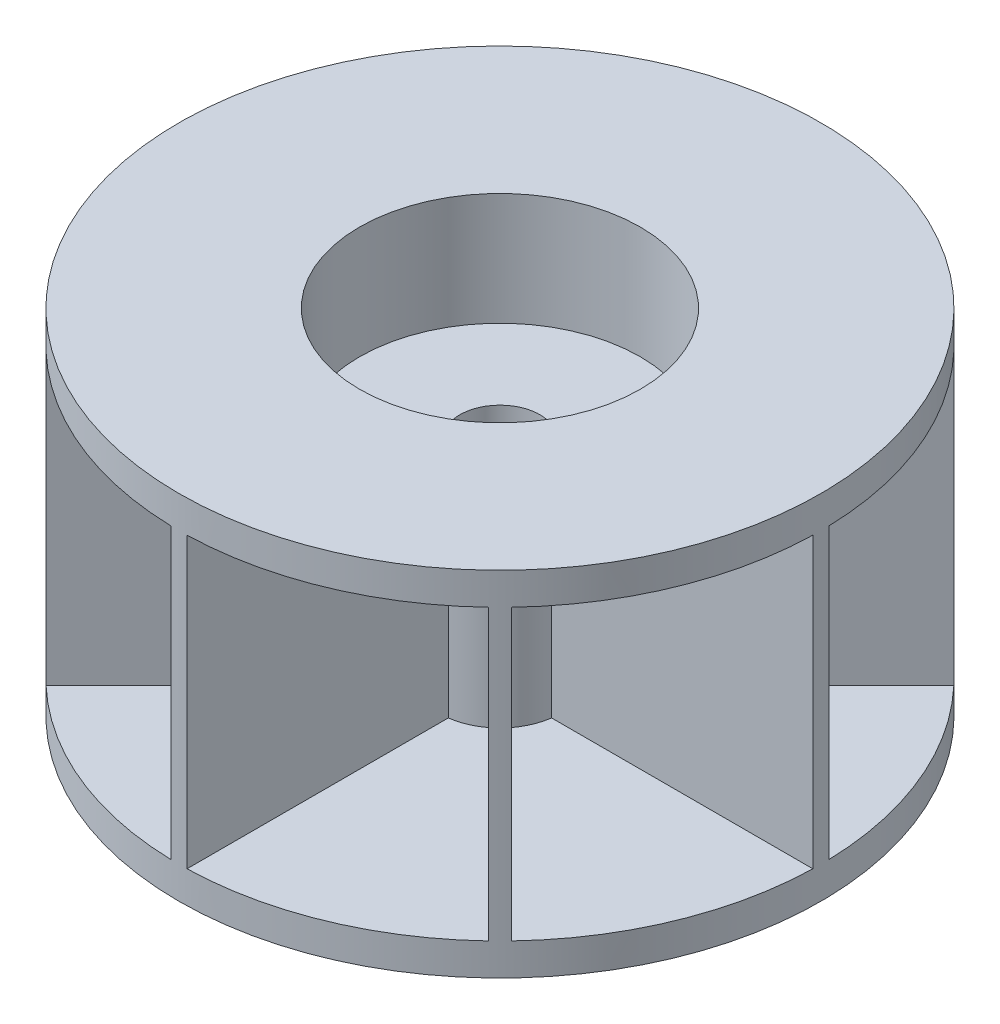
SolidWorks part; units mm, degrees
ref_plane "Front Plane" through (0, 0, 0) normal (0, 0, 1) x (1, 0, 0)
ref_plane "Top Plane" through (0, 0, 0) normal (0, 1, 0) x (1, 0, 0)
ref_plane "Right Plane" through (0, 0, 0) normal (1, 0, 0) x (0, 0, -1)
sketch "Sketch1" plane through (0, 0, 0) normal (0, 1, 0) x (1, 0, 0)
  circle A0 centre (0, 0) radius 3.175
  circle A1 centre (0, 0) radius 25.4
  dimension "D1" = 6.35
  dimension "D2" = 50.8
extrude "Boss-Extrude1" add sketch "Sketch1" along normal blind 2.54
sketch "Sketch2" plane through (0, 2.54, 0) normal (0, 1, 0) x (1, 0, 0)
  line L0 (0, 25.4) -> (0, 3.175)
  line L1 (-0.635, 25.3921) -> (-0.635, 3.1109)
  line L2 (0.635, 25.3921) -> (0.635, 3.1109)
  line L3 (18.4039, 17.5059) -> (2.6487, 1.7507)
  line L4 (17.5059, 18.4039) -> (1.7507, 2.6487)
  line L5 (25.3921, -0.635) -> (3.1109, -0.635)
  line L6 (25.3921, 0.635) -> (3.1109, 0.635)
  line L7 (17.5059, -18.4039) -> (1.7507, -2.6487)
  line L8 (18.4039, -17.5059) -> (2.6487, -1.7507)
  line L9 (-0.635, -25.3921) -> (-0.635, -3.1109)
  line L10 (0.635, -25.3921) -> (0.635, -3.1109)
  line L11 (-18.4039, -17.5059) -> (-2.6487, -1.7507)
  line L12 (-17.5059, -18.4039) -> (-1.7507, -2.6487)
  line L13 (-25.3921, 0.635) -> (-3.1109, 0.635)
  line L14 (-25.3921, -0.635) -> (-3.1109, -0.635)
  line L15 (-17.5059, 18.4039) -> (-1.7507, 2.6487)
  line L16 (-18.4039, 17.5059) -> (-2.6487, 1.7507)
  circle A0 centre (0, 0) radius 25.4 construction
  circle A1 centre (0, 0) radius 3.175 construction
  circle A2 centre (0, 0) radius 25.4
  circle A3 centre (0, 0) radius 3.175
  circle A4 centre (0, 0) radius 25.4 construction
  circle A5 centre (0, 0) radius 4.7625
  point P42 (0, 0)
  circle M4 centre (0, 0) radius 25.4
  circle M5 centre (0, 0) radius 3.175
  dimension "D1" = 0.635
  dimension "D4" = 9.525
  dimension "D3" = 8
  dimension "D2" = 0.635
extrude "Boss-Extrude4" add sketch "Sketch2" along normal blind 13.97 contours L1 L0 M4 M5 | L2 L0 M4 M5 | L4 L3 M4 M5 | L6 L5 M4 M5 | L8 L7 M4 M5 | L10 L9 M4 M5 | L12 L11 M4 M5 | L14 L13 M4 M5 | L16 L15 M4 M5 | L6 A5 L3 M5 | L5 A5 L6 M5 | L8 A5 L5 M5 | L7 A5 L8 M5 | L10 A5 L7 M5 | L9 A5 L10 M5 | L12 A5 L9 M5 | L11 A5 L12 M5 | L14 A5 L11 M5 | L13 A5 L14 M5 | L16 A5 L13 M5 | L15 A5 L16 M5 | L1 A5 L15 M5 | L0 A5 L1 M5 | L2 A5 L0 M5 | L4 A5 L2 M5 | L3 A5 L4 M5 region at (0.3176, 2.54, -15.0728) region at (-0.3176, 2.54, -15.0728) region at (0.3182, 2.54, -3.951) region at (-0.3182, 2.54, -3.951) region at (1.5388, 2.54, -3.7149) region at (-1.5388, 2.54, -3.7149) region at (10.6581, 2.54, -10.6581) region at (-10.6581, 2.54, -10.6581) region at (2.7938, 2.54, -2.7938) region at (-2.7938, 2.54, -2.7938) region at (3.7149, 2.54, -1.5388) region at (-3.7149, 2.54, -1.5388) region at (15.0728, 2.54, 0) region at (-15.0728, 2.54, 0) region at (3.951, 2.54, 0) region at (-3.951, 2.54, 0) region at (-3.7149, 2.54, 1.5388) region at (-10.6581, 2.54, 10.6581) region at (3.7149, 2.54, 1.5388) region at (-2.7938, 2.54, 2.7938) region at (10.6581, 2.54, 10.6581) region at (2.7938, 2.54, 2.7938) region at (-1.5388, 2.54, 3.7149) region at (0, 2.54, 15.0728) region at (1.5388, 2.54, 3.7149) region at (0, 2.54, 3.951)
sketch "Sketch5" plane through (0, 16.51, 0) normal (0, 1, 0) x (1, 0, 0)
  line L0 (0.635, -11.0943) -> (0.635, -25.3921)
  line L1 (0.635, -25.3921) -> (0.635, -4.72) construction
  line L2 (-0.635, -25.3921) -> (-0.635, -11.0943)
  line L3 (-0.635, -25.3921) -> (-0.635, -4.72) construction
  line L4 (-7.3959, -8.2939) -> (-17.5059, -18.4039)
  line L5 (-18.4039, -17.5059) -> (-8.2939, -7.3959)
  line L6 (-11.0943, -0.635) -> (-25.3921, -0.635)
  line L7 (-25.3921, 0.635) -> (-11.0943, 0.635)
  line L8 (-8.2939, 7.3959) -> (-18.4039, 17.5059)
  line L9 (-17.5059, 18.4039) -> (-7.3959, 8.2939)
  line L10 (-0.635, 11.0943) -> (-0.635, 25.3921)
  line L11 (0.635, 25.3921) -> (0.635, 11.0943)
  line L12 (7.3959, 8.2939) -> (17.5059, 18.4039)
  line L13 (18.4039, 17.5059) -> (8.2939, 7.3959)
  line L14 (11.0943, 0.635) -> (25.3921, 0.635)
  line L15 (25.3921, -0.635) -> (11.0943, -0.635)
  line L16 (8.2939, -7.3959) -> (18.4039, -17.5059)
  line L17 (17.5059, -18.4039) -> (7.3959, -8.2939)
  circle A0 centre (0, 0) radius 3.175
  circle A1 centre (0, 0) radius 11.1125
  circle A2 centre (0, 0) radius 25.4
  circle A3 centre (0, 0) radius 12.7
  point P45 (0, 0)
  circle M3 centre (0, 0) radius 3.175
  line M4 (17.5059, 18.4039) -> (2.8885, 3.7865)
  arc M5 (2.8885, 3.7865) -> (0.635, 4.72) centre (0, 0) ccw
  line M6 (0.635, 4.72) -> (0.635, 25.3921)
  arc M7 (0.635, 25.3921) -> (-0.635, 25.3921) centre (0, 0) ccw
  line M8 (-0.635, 25.3921) -> (-0.635, 4.72)
  arc M9 (-0.635, 4.72) -> (-2.8885, 3.7865) centre (0, 0) ccw
  line M10 (-2.8885, 3.7865) -> (-17.5059, 18.4039)
  arc M11 (-17.5059, 18.4039) -> (-18.4039, 17.5059) centre (0, 0) ccw
  line M12 (-18.4039, 17.5059) -> (-3.7865, 2.8885)
  arc M13 (-3.7865, 2.8885) -> (-4.72, 0.635) centre (0, 0) ccw
  line M14 (-4.72, 0.635) -> (-25.3921, 0.635)
  arc M15 (-25.3921, 0.635) -> (-25.3921, -0.635) centre (0, 0) ccw
  line M16 (-25.3921, -0.635) -> (-4.72, -0.635)
  arc M17 (-4.72, -0.635) -> (-3.7865, -2.8885) centre (0, 0) ccw
  line M18 (-3.7865, -2.8885) -> (-18.4039, -17.5059)
  arc M19 (-18.4039, -17.5059) -> (-17.5059, -18.4039) centre (0, 0) ccw
  line M20 (-17.5059, -18.4039) -> (-2.8885, -3.7865)
  arc M21 (-2.8885, -3.7865) -> (-0.635, -4.72) centre (0, 0) ccw
  line M22 (-0.635, -4.72) -> (-0.635, -25.3921)
  arc M23 (-0.635, -25.3921) -> (0.635, -25.3921) centre (0, 0) ccw
  line M24 (0.635, -25.3921) -> (0.635, -4.72)
  arc M25 (0.635, -4.72) -> (2.8885, -3.7865) centre (0, 0) ccw
  line M26 (2.8885, -3.7865) -> (17.5059, -18.4039)
  arc M27 (17.5059, -18.4039) -> (18.4039, -17.5059) centre (0, 0) ccw
  line M28 (18.4039, -17.5059) -> (3.7865, -2.8885)
  arc M29 (3.7865, -2.8885) -> (4.72, -0.635) centre (0, 0) ccw
  line M30 (4.72, -0.635) -> (25.3921, -0.635)
  arc M31 (25.3921, -0.635) -> (25.3921, 0.635) centre (0, 0) ccw
  line M32 (25.3921, 0.635) -> (4.72, 0.635)
  arc M33 (4.72, 0.635) -> (3.7865, 2.8885) centre (0, 0) ccw
  line M34 (3.7865, 2.8885) -> (18.4039, 17.5059)
  arc M35 (18.4039, 17.5059) -> (17.5059, 18.4039) centre (0, 0) ccw
  dimension "D1" = 22.225
  dimension "D3" = 1.5875
  dimension "D2" = 8
extrude "Boss-Extrude6" add sketch "Sketch5" along normal blind 2.54 contours A1 M28 M30 M29 | A1 M26 M28 M29 M30 M32 M33 M34 M4 M5 M6 M8 M9 M10 M12 M13 M14 M16 M17 M18 M20 M21 M22 M24 M25 M3 | A1 M24 M26 M25 | A1 M20 M22 M21 | A1 M16 M18 M17 | A1 M12 M14 M13 | A1 M8 M10 M9 | A1 M4 M6 M5 | A1 M32 M34 M33 region at (3.1868, 16.51, 7.6936) region at (0, 16.51, 10.7982) region at (-3.1868, 16.51, 7.6936) region at (7.6936, 16.51, 3.1868) region at (-7.6936, 16.51, 3.1868) region at (-7.6936, 16.51, -3.1868) region at (7.6936, 16.51, -3.1868) region at (-3.1868, 16.51, -7.6936) region at (3.1868, 16.51, -7.6936)
extrude "Boss-Extrude7" add sketch "Sketch5<4>" along normal blind 8.89 contours A1 M22 M23 M24 | A1 M26 M27 M28 | A1 M30 M31 M32 | A1 M34 M35 M4 | A1 M6 M7 M8 | A1 M10 M11 M12 | A1 M14 M15 M16 | A1 M18 M19 M20 | L16 A3 A1 M30 | A3 L16 A1 M26 | L0 A3 A1 M26 | A3 L0 A1 M22 | L4 A3 A1 M22 | A3 L4 A1 M18 | L6 A3 A1 M18 | A3 L6 A1 M14 | L8 A3 A1 M14 | A3 L8 A1 M10 | L10 A3 A1 M10 | A3 L10 A1 M6 | L12 A3 A1 M6 | A3 L12 A1 M34 | L14 A3 A1 M34 | A3 L14 A1 M30 region at (4.477, 16.51, 10.8084) region at (0, 16.51, 11.9006) region at (0, 16.51, 19.046) region at (-4.477, 16.51, 10.8084) region at (8.415, 16.51, 8.415) region at (13.4676, 16.51, 13.4676) region at (-8.415, 16.51, 8.415) region at (10.8084, 16.51, 4.477) region at (-13.4676, 16.51, 13.4676) region at (-10.8084, 16.51, 4.477) region at (11.9006, 16.51, 0) region at (19.046, 16.51, 0) region at (-11.9006, 16.51, 0) region at (-19.046, 16.51, 0) region at (-10.8084, 16.51, -4.477) region at (10.8084, 16.51, -4.477) region at (-8.415, 16.51, -8.415) region at (8.415, 16.51, -8.415) region at (-13.4676, 16.51, -13.4676) region at (13.4676, 16.51, -13.4676) region at (-4.477, 16.51, -10.8084) region at (4.477, 16.51, -10.8084) region at (0, 16.51, -11.9006) region at (0, 16.51, -19.046)
sketch "Sketch5<4>" plane through (0, 16.51, 0) normal (0, 1, 0) x (1, 0, 0) same geometry as "Sketch5"
sketch "Sketch6" plane through (0, 25.4, 0) normal (0, 1, 0) x (1, 0, 0)
  circle A0 centre (0, 0) radius 11.1125
  circle A1 centre (0, 0) radius 25.4
extrude "Boss-Extrude8" add sketch "Sketch6" along normal blind 2.54
